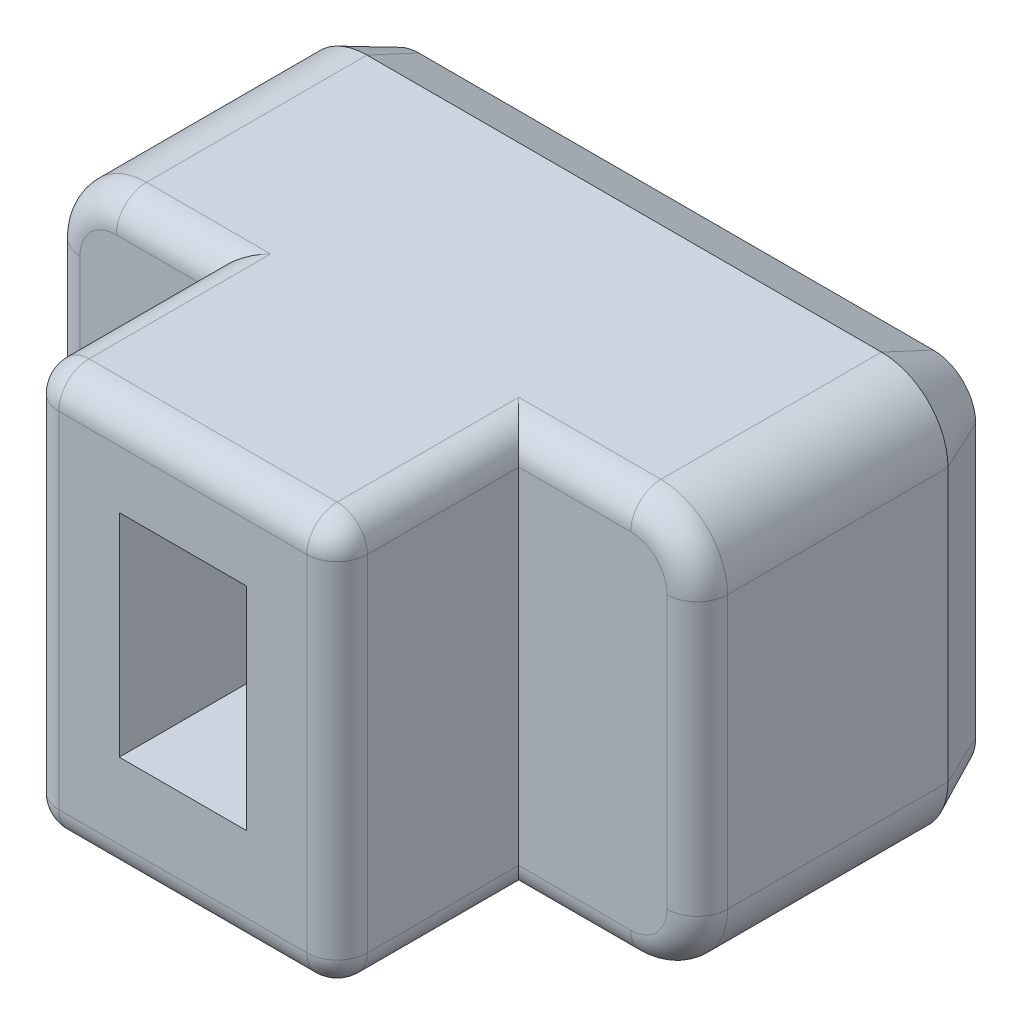
SolidWorks part; units mm, degrees
ref_plane "Plan de face" through (0, 0, 0) normal (0, 0, 1) x (1, 0, 0)
ref_plane "Plan de dessus" through (0, 0, 0) normal (0, 1, 0) x (1, 0, 0)
ref_plane "Plan de droite" through (0, 0, 0) normal (1, 0, 0) x (0, 0, -1)
sketch "Esquisse2" plane through (0, 0, 0) normal (0, 0, 1) x (1, 0, 0)
  line L1 (1.1, 0) -> (9.6, 0)
  line L2 (0, 1.1) -> (0, 5.6)
  line L3 (1.1, 6.7) -> (9.6, 6.7)
  line L4 (10.7, 1.1) -> (10.7, 5.6)
  arc A0 (9.6, 6.7) -> (10.7, 5.6) centre (9.6, 5.6) cw
  arc A1 (9.6, 0) -> (10.7, 1.1) centre (9.6, 1.1) ccw
  arc A2 (1.1, 0) -> (0, 1.1) centre (1.1, 1.1) cw
  arc A3 (0, 5.6) -> (1.1, 6.7) centre (1.1, 5.6) cw
  point P7 (10.7, 6.7)
  point P12 (0, 0)
  point P15 (0, 6.7)
  dimension "D3" = 1.1
  dimension "D1" = 10.7
  dimension "D2" = 6.7
extrude "Boss.-Extru.1" add sketch "Esquisse2" along normal blind 8
sketch "Esquisse3" plane through (0, 0, 8) normal (0, 0, 1) x (1, 0, 0)
  line L0 (0, 5.6) -> (0, 1.1) construction
  line L1 (4.15, 5.25) -> (6.25, 5.25)
  line L2 (4.15, 5.25) -> (4.15, 1.75)
  line L3 (4.15, 1.75) -> (6.25, 1.75)
  line L4 (6.25, 5.25) -> (6.25, 1.75)
  line L5 (10.7, 1.1) -> (10.7, 5.6) construction
  line L6 (9.6, 6.7) -> (1.1, 6.7) construction
  line L7 (1.1, 0) -> (9.6, 0) construction
  dimension "D1" = 2.1
  dimension "D2" = 3.5
  dimension "D3" = 4.15
  dimension "D4" = 4.45
  dimension "D5" = 1.45
  dimension "D6" = 1.75
extrude "Enlèv. mat.-Extru.1" cut sketch "Esquisse3" against normal blind 3
sketch "Esquisse4" plane through (0, 0, 8) normal (0, 0, 1) x (1, 0, 0)
  line L0 (2.65, 6.7) -> (2.65, 0)
  line L1 (9.6, 6.7) -> (1.1, 6.7) construction
  line L2 (1.1, 0) -> (9.6, 0) construction
  line L3 (2.65, 0) -> (7.75, 0)
  line L4 (7.75, 0) -> (7.75, 6.7)
  line L5 (7.75, 6.7) -> (2.65, 6.7)
  line L6 (4.15, 5.25) -> (4.15, 1.75) construction
  line L7 (6.25, 1.75) -> (6.25, 5.25) construction
  dimension "D1" = 1.5
  dimension "D2" = 1.5
extrude "Enlèv. mat.-Extru.2" cut sketch "Esquisse4" against normal blind 3 flip side to cut
fillet "Congé1" radius 0.5 18 edges at (8.675, 0, 5) (10.3778, 0.3222, 5) (10.7, 3.35, 5) (10.3778, 6.3778, 5) (1.875, 6.7, 5) (0.3222, 6.3778, 5) (1.875, 0, 5) (0.3222, 0.3222, 5) (7.75, 6.7, 6.5) (2.65, 6.7, 6.5) (7.75, 0, 6.5) (2.65, 0, 6.5) (2.65, 3.35, 8) (5.2, 6.7, 8) (7.75, 3.35, 8) (5.2, 0, 8) (8.675, 6.7, 5) (0, 3.35, 5)
chamfer "Chanfrein1" distance 0.4 angle 65 8 edges at (5.35, 0, 0) (10.3778, 0.3222, 0) (0.3222, 0.3222, 0) (10.7, 3.35, 0) (0, 3.35, 0) (10.3778, 6.3778, 0) (0.3222, 6.3778, 0) (5.35, 6.7, 0) first distance on face at (5.35, 3.35, 0)
ref_plane "Plan1" through (0, 0, 0.2) normal (0, 0, 1) x (1, 0, 0)
sketch "Esquisse5" plane through (0, 0, 0.2) normal (0, 0, 1) x (1, 0, 0)
  line L0 (-0.9378, 5.3566) -> (11.6517, 5.3566) construction
  text T0 "REV" font "Century Gothic" height 4
extrude "Enlèv. mat.-Extru.3" cut sketch "Esquisse5" against normal blind 0.3
extrude "Boss.-Extru.2" add sketch "Esquisse5<3>" against normal blind 0.2 from offset 0.2 offset against normal yes
sketch "Esquisse5<3>" plane through (0, 0, 0.2) normal (0, 0, 1) x (1, 0, 0) same geometry as "Esquisse5"
